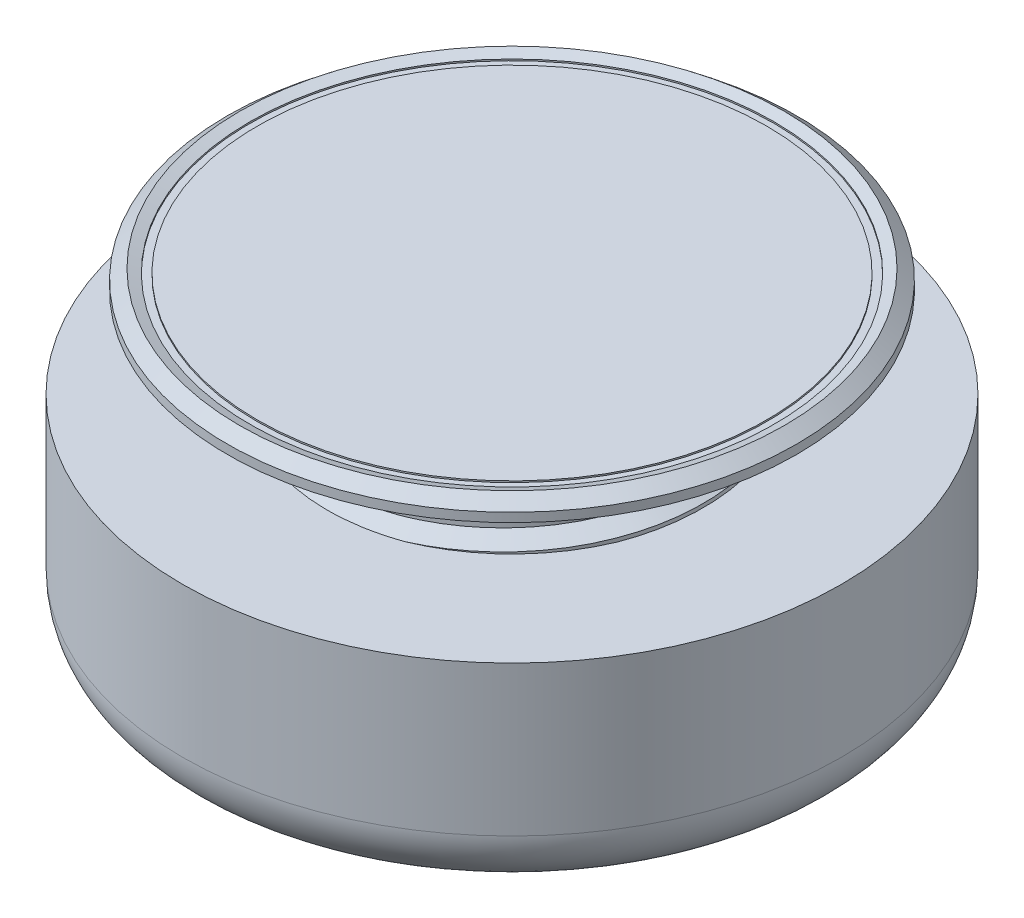
SolidWorks part; units mm, degrees
ref_plane "前视基准面" through (0, 0, 0) normal (0, 0, 1) x (1, 0, 0)
ref_plane "上视基准面" through (0, 0, 0) normal (0, 1, 0) x (1, 0, 0)
ref_plane "右视基准面" through (0, 0, 0) normal (1, 0, 0) x (0, 0, -1)
sketch "草图1" plane through (0, 0, 0) normal (0, 1, 0) x (1, 0, 0)
  circle A0 centre (0, 0) radius 11
  dimension "D1" = 22
extrude "凸台-拉伸1" add sketch "草图1" along normal blind 7
sketch "草图2" plane through (0, 7, 0) normal (0, 1, 0) x (1, 0, 0)
  circle A0 centre (0, 0) radius 6
  dimension "D1" = 12
extrude "凸台-拉伸2" add sketch "草图2" along normal blind 3
fillet "圆角1" radius 2 1 edges at (0, 0, 11)
thread "螺纹线1" pitch 1 method extrude profile "螺纹线轮廓1" start angle 0, offset 0, length 3, pitch 1, diameter 12
ref_plane "基准面1" through (-6, 10, 0) normal (0, 0, 1) x (-1, 0, 0)
sketch "螺纹线轮廓1" plane through (-6, 10, 0) normal (0, 0, 1) x (-1, 0, 0)
  line L0 (0, 0) -> (0, 1) construction
  line L1 (0, 0) -> (0.5413, 0.3125)
  line L2 (0.5413, 0.3125) -> (0.5413, 0.4375)
  line L3 (0.5413, 0.4375) -> (0, 0.75)
  line L4 (0.5413, 0.375) -> (0, 0.375) construction
  line L11 (0, 0) -> (0, 0.75)
  point P2 (0, 0)
  dimension "Pitch" = 1
  dimension "Profile_Angle" = 60
  dimension "Profile_Land" = 0.125
  dimension "Profile_Height" = 0.5413
sketch "草图7" plane through (0, 0, 0) normal (0, 0, 1) x (1, 0, 0)
  line L0 (0, 10) -> (-9.5, 10)
  line L1 (6, 10) -> (-6, 10) construction
  line L2 (-9.5, 10) -> (-9.5, 10.3)
  line L3 (-9.5, 10.3) -> (-9.0891, 10.6325)
  line L4 (-9.0891, 10.6325) -> (-8.75, 10.5)
  line L5 (-8.75, 10.5) -> (0, 10.5)
  line L6 (0, 10.5) -> (0, 10)
  dimension "D1" = 9.5
  dimension "D2" = 0.3
  dimension "D3" = 0.5
  dimension "D4" = 0.75
revolve "旋转1" add sketch "草图7" angle 360 about L6
sketch "草图9" plane through (0, 0, 0) normal (0, 0, 1) x (1, 0, 0)
  line L0 (8.75, 10.5) -> (-8.75, 10.5) construction
  line L1 (-9.5, 10.3) -> (-9.5, 10) construction
  line L2 (0, -0.9955) -> (0, 19.585) construction
  line L3 (-8.75, 10.5) -> (-8.5, 10.5)
  line L4 (-8.75, 10.5) -> (-8.75, 10.45)
  line L5 (-8.75, 10.45) -> (-8.5, 10.45)
  line L6 (-8.5, 10.5) -> (-8.5, 10.45)
  point P0 (-8.75, 10.5)
  dimension "D1" = 0.75
  dimension "D2" = 0.25
  dimension "D3" = 0.05
revolve "切除-旋转1" cut sketch "草图9" angle 360 about L2
